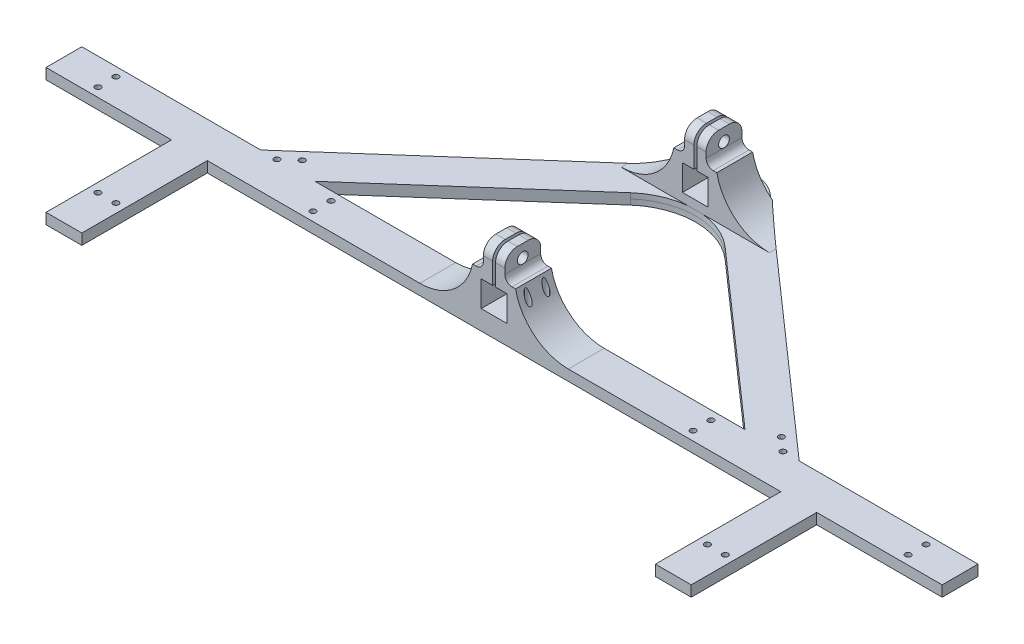
SolidWorks part; units mm, degrees
ref_plane "前视基准面" through (0, 0, 0) normal (0, 0, 1) x (1, 0, 0)
ref_plane "上视基准面" through (0, 0, 0) normal (0, 1, 0) x (1, 0, 0)
ref_plane "右视基准面" through (0, 0, 0) normal (1, 0, 0) x (0, 0, -1)
sketch "草图1" plane through (0, 0, 0) normal (0, 1, 0) x (1, 0, 0)
  line L1 (-125, 5) -> (125, 5)
  line L2 (-125, 5) -> (-125, -5)
  line L3 (-125, -5) -> (125, -5)
  line L4 (125, 5) -> (125, -5)
  line L5 (-125, 5) -> (125, -5) construction
  line L6 (-125, -5) -> (125, 5) construction
  point P0 (0, 0)
  dimension "D1" = 250
  dimension "D2" = 10
extrude "凸台-拉伸1" add sketch "草图1" along normal blind 1.5
sketch "草图22" plane through (0, 0, 0) normal (0, -1, 0) x (1, 0, 0)
  line L0 (0, 107.0541) -> (0, -222.8841) construction
  line L1 (0, 0) -> (-60, 0)
  line L2 (-125, 5) -> (125, 5) construction
  line L4 (125, -5) -> (-125, -5) construction
  line L5 (60, 0) -> (60, -5)
  line L6 (-60, -5) -> (0, -57.915)
  line L7 (0, -57.915) -> (60, -5)
  line L8 (-75.1186, -5) -> (0, -71.2484)
  line L9 (0, -71.2484) -> (75.1186, -5)
  line L10 (-60, -5) -> (-75.1186, -5)
  line L11 (60, -5) -> (75.1186, -5)
  line M16 (-125, -5) -> (125, -5)
  dimension "D1" = 60
  dimension "D2" = 80
  dimension "D3" = 10
extrude "凸台-拉伸10" add sketch "草图22" against normal blind 1.5 separate body contours L0 L6 L8 M16 | L7 L0 L9 M16 region at (33.9206, 0, -34.9152) region at (-33.9206, 0, -34.9152)
fillet "圆角1" radius 10 1 edges at (0, 0.75, -71.2484)
fillet "圆角2" radius 20 1 edges at (0, 0.75, -57.915)
sketch "草图24" plane through (0, 1.5, 0) normal (0, 1, 0) x (1, 0, 0)
  line L1 (-10, 5) -> (10, 5)
  line L2 (-10, 5) -> (-10, -5)
  line L3 (-10, -5) -> (10, -5)
  line L4 (10, 5) -> (10, -5)
  line L5 (-10, 5) -> (10, -5) construction
  line L6 (-10, -5) -> (10, 5) construction
  point P0 (0, 0)
  dimension "D1" = 20
  dimension "D2" = 10
extrude "凸台-拉伸11" add sketch "草图24" along normal blind 20
sketch "草图25" plane through (0, 0, 5) normal (0, 0, 1) x (1, 0, 0)
  line L1 (0, 23.6125) -> (0, -2.2867) construction
sketch "草图26" plane through (0, 1.5, 0) normal (0, 1, 0) x (1, 0, 0)
  line L0 (0, 141.3842) -> (0, -41.294) construction
  line L2 (-11, 61.1419) -> (11, 61.1419)
  line L3 (-11, 61.1419) -> (-11, 51.1419)
  line L4 (-11, 51.1419) -> (11, 51.1419)
  line L5 (11, 61.1419) -> (11, 51.1419)
  line L6 (-11, 61.1419) -> (11, 51.1419) construction
  line L7 (-11, 51.1419) -> (11, 61.1419) construction
  point P6 (0, 56.1419)
  dimension "D1" = 22
  dimension "D2" = 10
sketch "草图41" plane through (0, 0, 5) normal (0, 0, 1) x (1, 0, 0)
  line L0 (125, 0.75) -> (-129.8236, 0.75) construction
  line L1 (125, 1.5) -> (125, 0) construction
  line L2 (125, 0.75) -> (85, 0.75)
  line L4 (80, 1.5) -> (90, 1.5)
  line L5 (80, 1.5) -> (80, 0)
  line L6 (80, 0) -> (90, 0)
  line L7 (90, 1.5) -> (90, 0)
  line L8 (80, 1.5) -> (90, 0) construction
  line L9 (80, 0) -> (90, 1.5) construction
  line M8 (-125, 0) -> (125, 0)
  line M10 (125, 1.5) -> (10, 1.5)
  dimension "D1" = 40
  dimension "D2" = 10
  dimension "D3" = 1.5
extrude "凸台-拉伸13" add sketch "草图41" along normal blind 35 contours L7 L5 M10 M8 region at (85, 1.3989, 5)
sketch "草图42" plane through (0, 0, 5) normal (0, 0, 1) x (1, 0, 0)
  line L0 (-125, 0.75) -> (-85, 0.75)
  line L1 (-125, 1.5) -> (-125, 0) construction
  line L3 (-90, 1.5) -> (-80, 1.5)
  line L4 (-90, 1.5) -> (-90, 0)
  line L5 (-90, 0) -> (-80, 0)
  line L6 (-80, 1.5) -> (-80, 0)
  line L7 (-90, 1.5) -> (-80, 0) construction
  line L8 (-90, 0) -> (-80, 1.5) construction
  line M14 (-10, 1.5) -> (-125, 1.5)
  line M16 (-125, 0) -> (80, 0)
  dimension "D1" = 40
  dimension "D2" = 10
  dimension "D3" = 1.5
extrude "凸台-拉伸14" add sketch "草图42" along normal blind 35 contours L6 L4 M14 M16 region at (-85, 1.3989, 5)
sketch "草图57" plane through (0, 0, 0) normal (0, -1, 0) x (-1, 0, 0)
  line L0 (125, -5) -> (90, -5)
  line L1 (90, -5) -> (90, -40)
  line L2 (90, -40) -> (80, -40)
  line L3 (80, -40) -> (80, -5)
  line L4 (80, -5) -> (-80, -5)
  line L5 (-80, -5) -> (-80, -40)
  line L6 (-80, -40) -> (-90, -40)
  line L7 (-90, -40) -> (-90, -5)
  line L8 (-90, -5) -> (-125, -5)
  line L9 (-125, -5) -> (-125, 5)
  line L10 (-125, 5) -> (-75.1186, 5)
  line L11 (-75.1186, 5) -> (-6.6144, 65.415)
  line L12 (-6.6144, 65.415) -> (0, 71.2484)
  line L13 (0, 71.2484) -> (6.6144, 65.415)
  line L14 (6.6144, 65.415) -> (75.1186, 5)
  line L15 (75.1186, 5) -> (125, 5)
  line L16 (125, 5) -> (125, -5)
  line L17 (60, 5) -> (-60, 5)
  line L18 (-60, 5) -> (0, 57.915)
  line L19 (0, 57.915) -> (60, 5)
extrude "凸台-拉伸15" add sketch "草图57" along normal blind 1.5
fillet "圆角5" radius 20 1 edges at (0, -0.75, -57.915)
fillet "圆角6" radius 10 1 edges at (0, -0.75, -71.2484)
sketch "草图58" plane through (0, -1.5, 0) normal (0, -1, 0) x (1, 0, 0)
  line L0 (0, 12.1149) -> (0, -11.1082) construction
  line L1 (0, 0) -> (7, 0)
  line L2 (7, 0) -> (7, 2.5)
  line L3 (7, 0) -> (7, -2.5)
  line L4 (127.0686, 0) -> (101.0767, 0) construction
  line L5 (125, 0) -> (113, 0)
  line L6 (125, -5) -> (125, 5) construction
  line L7 (113, 0) -> (113, 2.5)
  line L8 (113, 0) -> (113, -2.5)
  line L10 (-125, 5) -> (-125, -5)
  line L11 (125, 5) -> (125, -5)
  line L12 (0, 0) -> (53, 0)
  line L14 (53, 0) -> (53, 2.5)
  line L15 (53, 0) -> (53, -2.5)
  line L16 (-85, 40) -> (-85, 28)
  line L17 (-80, 40) -> (-90, 40) construction
  line L18 (-85, 28) -> (-87.5, 28)
  line L19 (-85, 28) -> (-82.5, 28)
  circle A0 centre (7, -2.5) radius 0.8
  circle A1 centre (7, 2.5) radius 0.8
  circle A2 centre (113, 2.5) radius 0.8
  circle A3 centre (113, -2.5) radius 0.8
  circle A4 centre (-113, -2.5) radius 0.8
  circle A5 centre (-113, 2.5) radius 0.8
  circle A6 centre (53, 2.5) radius 0.8
  circle A7 centre (53, -2.5) radius 0.8
  circle A8 centre (-53, -2.5) radius 0.8
  circle A9 centre (-53, 2.5) radius 0.8
  circle A10 centre (-82.5, 28) radius 0.8
  circle A11 centre (-87.5, 28) radius 0.8
  circle A12 centre (82.5, 28) radius 0.8
  circle A13 centre (87.5, 28) radius 0.8
  dimension "D4" = 1.6
  dimension "D5" = 1.6
  dimension "D9" = 1.6
  dimension "D10" = 1.6
  dimension "D15" = 1.6
  dimension "D16" = 1.6
  dimension "D20" = 1.6
  dimension "D21" = 1.6
  dimension "D1" = 7
  dimension "D2" = 2.5
  dimension "D3" = 2.5
  dimension "D6" = 12
  dimension "D7" = 2.5
  dimension "D8" = 2.5
  dimension "D11" = 250
  dimension "D12" = 53
  dimension "D13" = 2.5
  dimension "D14" = 2.5
  dimension "D17" = 12
  dimension "D18" = 2.5
  dimension "D19" = 2.5
extrude "切除-拉伸52" cut sketch "草图58" against normal through all contours A5 | A4 | A11 | A10 | A9 | A8 | A0 | A1 | A6 | A7 | A2 | A3 | A12 | A13 region at (6.4503, -1.5, 3.0497) region at (7.5497, -1.5, -1.9503) region at (52.4503, -1.5, 3.0497) region at (53.5497, -1.5, -1.9503) region at (112.4503, -1.5, 3.0497) region at (113.5497, -1.5, -1.9503) region at (-88.2774, -1.5, 28) region at (-82.5, -1.5, 28.7774) region at (-113, -1.5, -2.5) region at (-113, -1.5, 2.5) region at (-53, -1.5, -2.5) region at (-53, -1.5, 2.5) region at (82.5, -1.5, 28) region at (87.5, -1.5, 28)
extrude "凸台-拉伸16" add sketch "草图26" along normal blind 20
sketch "草图59" plane through (0, 0, -61.1419) normal (0, 0, -1) x (-1, 0, 0)
  line L0 (0, 1.5376) -> (0, 4.0376)
  line L1 (0, 23.6125) -> (0, -2.2867) construction
  line L2 (0, 4.0376) -> (3.5, 4.0376)
  line L3 (3.5, 4.0376) -> (3.5, 11.0376)
  line L4 (3.5, 11.0376) -> (-3.5, 11.0376)
  line L5 (-3.5, 11.0376) -> (-3.5, 4.0376)
  line L6 (-3.5, 4.0376) -> (0, 4.0376)
  line L7 (0, 1.5376) -> (6, 1.5)
  line L8 (-11, 1.5) -> (11, 1.5) construction
  line L9 (6, 1.5) -> (6, 13.5)
  line L10 (6, 13.5) -> (-6, 13.5)
  line L11 (-6, 13.5) -> (-6, 1.5)
  line L12 (-6, 1.5) -> (0, 1.5376)
  line L14 (0, 13.5) -> (3, 13.5)
  line L18 (0, 13.5) -> (-3, 13.5)
  line L24 (0, 11.0376) -> (0.9278, 11.0376)
  line L26 (0, 13.5) -> (0.4, 13.5)
  line L27 (0, 13.5) -> (0, 20.5)
  line L28 (0, 20.5) -> (0.4, 20.5)
  line L29 (0.4, 13.5) -> (0.4, 20.5)
  line L30 (0, 13.5) -> (-0.4, 13.5)
  line L31 (0, 13.5) -> (0, 20.5)
  line L32 (0, 20.5) -> (-0.4, 20.5)
  line L33 (-0.4, 13.5) -> (-0.4, 20.5)
  line L34 (-0.4, 13.5) -> (0.4, 13.5)
  line L35 (-0.4, 13.5) -> (-0.4, 11.0376)
  line L36 (-0.4, 11.0376) -> (0.4, 11.0376)
  line L37 (0.4, 13.5) -> (0.4, 11.0376)
  line L38 (0, 13.5) -> (3, 13.5)
  line L39 (0, 13.5) -> (0, 20.5)
  line L40 (0, 20.5) -> (3, 20.5)
  line L41 (3, 13.5) -> (3, 20.5)
  line L42 (0, 13.5) -> (-3, 13.5)
  line L43 (0, 13.5) -> (0, 20.5)
  line L44 (0, 20.5) -> (-3, 20.5)
  line L45 (-3, 13.5) -> (-3, 20.5)
  line M21 (-11, 1.5) -> (11, 1.5)
  line M22 (11, 1.5) -> (11, 21.5)
  line M23 (11, 21.5) -> (-11, 21.5)
  line M24 (-11, 21.5) -> (-11, 1.5)
  dimension "D1" = 2.5
  dimension "D2" = 3.5
  dimension "D3" = 7
  dimension "D4" = 7
  dimension "D5" = 12
  dimension "D6" = 12
  dimension "D7" = 6
  dimension "D8" = 0.4
  dimension "D9" = 7
  dimension "D10" = 0.4
  dimension "D11" = 7
  dimension "D12" = 3
  dimension "D13" = 3
extrude "切除-拉伸53" cut sketch "草图59" against normal through all contours L10 L45 L44 L32 L28 L40 L41 L9 L11 M21 M22 M23 M24 | L5 L6 L2 L3 L4 L24 | L37 L14 L10 L35 L4 L24 | L33 L10 L27 L32 | L14 L29 L28 L27 region at (0, 7.5376, -61.1419) region at (-6.2973, 7.5, -61.1419) region at (0, 12.2688, -61.1419) region at (-0.2, 17, -61.1419) region at (0.2, 17, -61.1419)
fillet "圆角7" radius 15 2 edges at (6, 1.5, -56.1419) (-6, 1.5, -56.1419)
fillet "圆角8" radius 15 2 edges at (6, 1.5, 0) (-6, 1.5, 0)
fillet "圆角9" radius 3.5 8 edges at (-1.7, 20.5, 5) (1.7, 20.5, 5) (1.7, 20.5, -5) (-1.7, 20.5, -5) (-1.7, 20.5, -51.1419) (1.7, 20.5, -51.1419) (-1.7, 20.5, -61.1419) (1.7, 20.5, -61.1419)
sketch "草图60" plane through (-3, 0, 0) normal (-1, 0, 0) x (0, 0, 1)
  line L0 (-56.1419, 20.5) -> (-56.1419, 17) construction
  line L1 (-54.6419, 20.5) -> (-57.6419, 20.5) construction
  circle A0 centre (-56.1419, 17) radius 1.5
  dimension "D2" = 3
  dimension "D1" = 3.5
extrude "切除-拉伸54" cut sketch "草图60" against normal through all
sketch "草图61" plane through (-3, 0, 0) normal (-1, 0, 0) x (0, 0, 1)
  line L0 (0, 20.5) -> (0, 17) construction
  line L1 (1.5, 20.5) -> (-1.5, 20.5) construction
  circle A0 centre (0, 17) radius 1.5
  dimension "D2" = 3
  dimension "D1" = 3.5
extrude "切除-拉伸55" cut sketch "草图61" against normal through all
fillet "圆角10" radius 2 4 edges at (3, 13.5, -56.1419) (3, 13.5, 0) (-3, 13.5, 0) (-3, 13.5, -56.1419)
sketch "草图63" plane through (0, 1.5, 0) normal (0, 1, 0) x (1, 0, 0)
  line L0 (72.4633, 3.3417) -> (59.0753, 15.1489) construction
  line L1 (75.1186, 5) -> (64.3471, 14.4995) construction
  line L2 (20.6969, 52.9954) -> (75.1186, 5) construction
  line L3 (75.1186, 5) -> (70.583, 5) construction
  line L4 (0, -22.5098) -> (0, 28.2143) construction
  circle A0 centre (70.583, 5) radius 0.8
  circle A1 centre (66.833, 8.3072) radius 0.8
  circle A2 centre (-66.833, 8.3072) radius 0.8
  circle A3 centre (-70.583, 5) radius 0.8
  point P10 (66.833, 8.3072)
  dimension "D2" = 1.6
  dimension "D4" = 1.6
  dimension "D1" = 3
  dimension "D3" = 5
extrude "切除-拉伸56" cut sketch "草图63" against normal through all
sketch "草图64" plane through (0, 0, 5) normal (0, 0, 1) x (1, 0, 0)
  line L1 (3.5, 11.0376) -> (3.6, 11.0376)
  line L2 (3.5, 11.0376) -> (3.5, 3.9376)
  line L3 (3.5, 3.9376) -> (3.6, 3.9376)
  line L4 (3.6, 11.0376) -> (3.6, 3.9376)
  line L5 (3.5, 4.0376) -> (-3.6, 4.0376)
  line L6 (3.5, 4.0376) -> (3.5, 3.9376)
  line L7 (3.5, 3.9376) -> (-3.6, 3.9376)
  line L8 (-3.6, 4.0376) -> (-3.6, 3.9376)
  line L9 (-3.5, 4.0376) -> (-3.6, 4.0376)
  line L10 (-3.5, 4.0376) -> (-3.5, 11.1376)
  line L11 (-3.5, 11.1376) -> (-3.6, 11.1376)
  line L12 (-3.6, 4.0376) -> (-3.6, 11.1376)
  line L13 (-3.5, 11.0376) -> (3.6, 11.0376)
  line L14 (-3.5, 11.0376) -> (-3.5, 11.1376)
  line L15 (-3.5, 11.1376) -> (3.6, 11.1376)
  line L16 (3.6, 11.0376) -> (3.6, 11.1376)
  line M12 (-0.4, 11.0376) -> (-0.4, 17)
  line M28 (0.4, 17) -> (0.4, 11.0376)
  line M29 (0.4, 11.0376) -> (3.5, 11.0376)
  line M32 (-3.5, 4.0376) -> (-3.5, 11.0376)
  line M33 (-3.5, 11.0376) -> (-0.4, 11.0376)
  dimension "D1" = 7.1
  dimension "D2" = 0.1
  dimension "D3" = 7.1
  dimension "D4" = 0.1
  dimension "D5" = 7.1
  dimension "D6" = 0.1
  dimension "D7" = 7.1
extrude "切除-拉伸57" cut sketch "草图64" against normal through all contours L12 L5 L10 L11 M32 | L15 L10 M33 M12 | L1 L16 L15 M28 M29 | L2 L3 L4 L1 | L8 L7 L6 L5 region at (2, 11.0876, 5) region at (-3.55, 7.5876, 5) region at (-1.95, 11.0876, 5)
